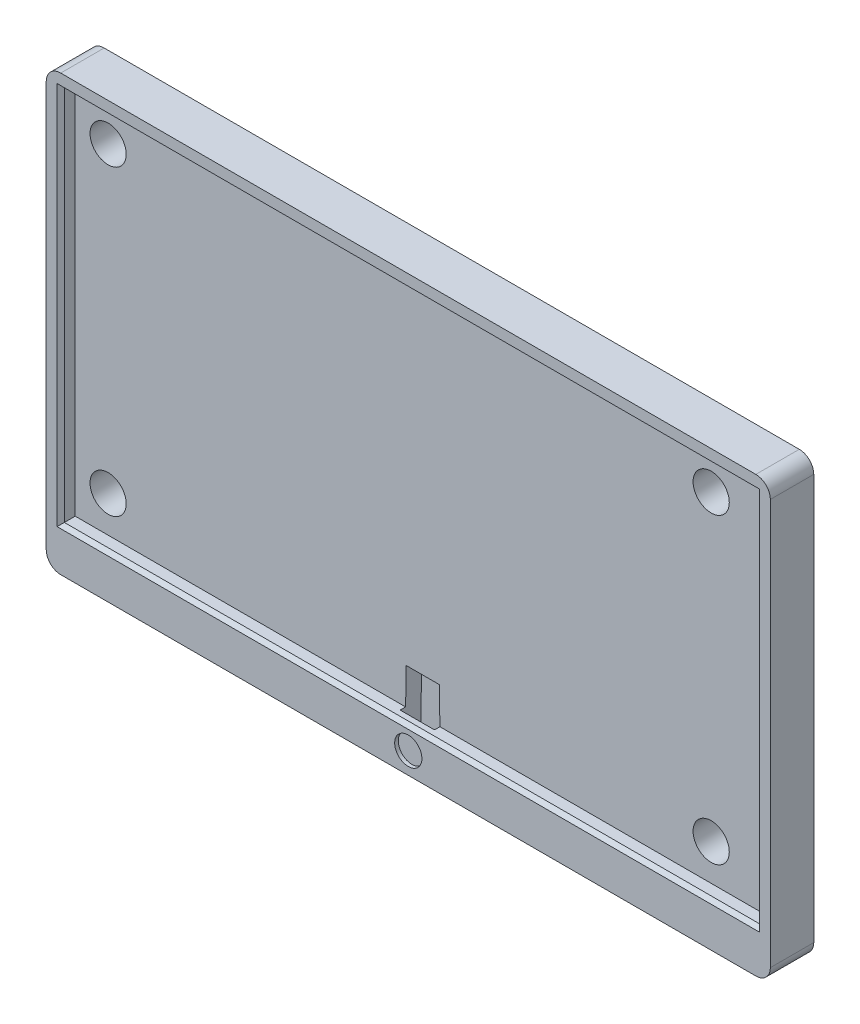
SolidWorks part; units mm, degrees
ref_plane "Front Plane" through (0, 0, 0) normal (0, 0, 1) x (1, 0, 0)
ref_plane "Top Plane" through (0, 0, 0) normal (0, 1, 0) x (1, 0, 0)
ref_plane "Right Plane" through (0, 0, 0) normal (1, 0, 0) x (0, 0, -1)
sketch "Sketch1" plane through (0, 0, 0) normal (0, 0, 1) x (1, 0, 0)
  line L0 (0, -3.3) -> (0, 3.3) construction
  line L1 (-50, 30) -> (50, 30)
  line L2 (-50, 30) -> (-50, -30)
  line L3 (-50, -30) -> (50, -30)
  line L4 (50, 30) -> (50, -30)
  line L5 (3.3, 0) -> (-3.3, 0) construction
  point P4 (0, 30)
  point P7 (-50, 0)
  dimension "D1" = 100
  dimension "D2" = 60
extrude "Boss-Extrude1" add sketch "Sketch1" along normal blind 3 and the other way blind 3
sketch "Sketch2" plane through (0, -30, 0) normal (0, -1, 0) x (1, 0, 0)
  line L0 (0, -3.3) -> (0, 3.3) construction
  line L1 (2.475, -1.15) -> (-2.475, -1.15)
  line L2 (2.475, -1.15) -> (2.475, 1.75)
  line L3 (2.475, 1.75) -> (-2.475, 1.75)
  line L4 (-2.475, -1.15) -> (-2.475, 1.75)
  line L6 (2.075, 0.25) -> (2.075, -0.25) construction
  line L8 (1.575, -0.75) -> (-1.575, -0.75) construction
  line L9 (-1.575, 0.75) -> (1.575, 0.75) construction
  point P4 (0, -1.15)
  dimension "D1" = 0.4
  dimension "D2" = 0.4
  dimension "D3" = 1
extrude "Cut-Extrude1" cut sketch "Sketch2" against normal blind 11
draft "Draft1" type of draft neutral plane draft angle 1 faces to draft 2 face at (-2.475, -24.5, 0.3) face at (2.475, -24.5, 0.3) neutral plane through (-50, -30, -3) neutral plane normal (0, -1, 0) parameters "D1"=1
sketch "Sketch3" plane through (0, 0, 3) normal (0, 0, 1) x (1, 0, 0)
  line L0 (50, 30) -> (-50, 30) construction
  line L1 (-48, 28) -> (48, 28)
  line L2 (-48, 28) -> (-48, -24)
  line L3 (-48, -24) -> (48, -24)
  line L4 (48, 28) -> (48, -24)
  line L5 (-50, 30) -> (-50, -30) construction
  line L7 (0, -3.3) -> (0, 3.3) construction
  line L8 (-50, -30) -> (50, -30) construction
  point P11 (0, 28)
  dimension "D1" = 2
  dimension "D2" = 2
  dimension "D3" = 6
extrude "Cut-Extrude2" cut sketch "Sketch3" against normal blind 2
fillet "Fillet1" radius 2 4 edges at (-50, 30, 0) (50, -30, 0) (50, 30, 0) (-50, -30, 0)
sketch "Sketch4" plane through (0, 0, 1) normal (0, 0, 1) x (1, 0, 0)
  line L1 (47.8, 27.8) -> (-47.8, 27.8) construction
  line L2 (-48, -24) -> (48, -24) construction
  circle A0 centre (-43.4539, 22.8) radius 2.5
  circle A1 centre (-43.4539, -19) radius 2.5
  circle A2 centre (39.8328, -19) radius 2.5
  circle A3 centre (39.8328, 22.8) radius 2.5
  dimension "D1" = 5
  dimension "D2" = 5
  dimension "D3" = 5
  dimension "D4" = 5
  dimension "D5" = 5
  dimension "D6" = 5
extrude "Cut-Extrude3" cut sketch "Sketch4" against normal through all
chamfer "Chamfer1" distance 0.5 angle 45 4 edges at (48, 2, 3) (0, 28, 3) (-48, 2, 3) (0, -24, 3)
sketch "Sketch5" plane through (0, 0, 3) normal (0, 0, 1) x (1, 0, 0)
  line L0 (0, -3.3) -> (0, 3.3) construction
  circle A0 centre (0, -27.0563) radius 1.8826
extrude "Cut-Extrude4" cut sketch "Sketch5" against normal blind 0.5
